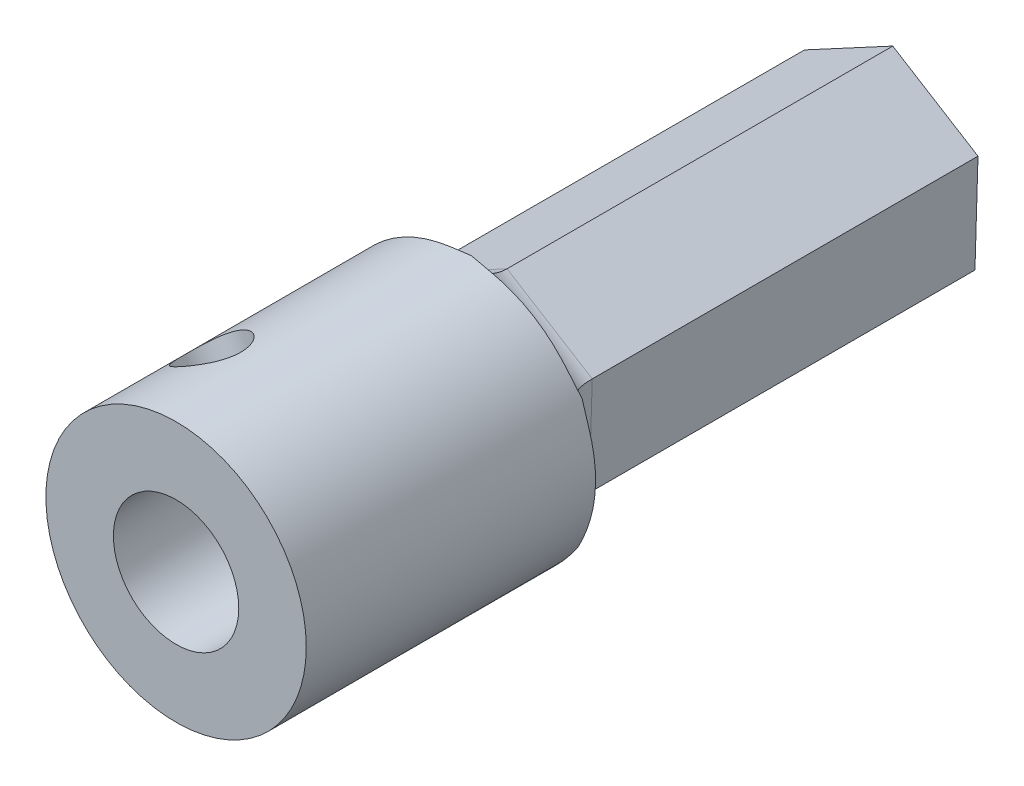
SolidWorks part; units mm, degrees
ref_plane "Front Plane" through (0, 0, 0) normal (0, 0, 1) x (1, 0, 0)
ref_plane "Top Plane" through (0, 0, 0) normal (0, 1, 0) x (1, 0, 0)
ref_plane "Right Plane" through (0, 0, 0) normal (1, 0, 0) x (0, 0, -1)
sketch "Sketch1" plane through (0, 0, 0) normal (0, 0, 1) x (1, 0, 0)
  line L1 (4.5768, 2.4602) -> (0.1578, 5.1938)
  line L2 (0.1578, 5.1938) -> (-4.419, 2.7335)
  line L3 (-4.419, 2.7335) -> (-4.5768, -2.4602)
  line L4 (-4.5768, -2.4602) -> (-0.1578, -5.1938)
  line L5 (-0.1578, -5.1938) -> (4.419, -2.7335)
  line L6 (4.419, -2.7335) -> (4.5768, 2.4602)
  circle A0 centre (0, 0) radius 4.5 construction
  dimension "D1" = 9
extrude "Boss-Extrude1" add sketch "Sketch1" along normal blind 22 contours L2 L3 L4 L5 L6 L1
sketch "Sketch2" plane through (0, 0, 22) normal (0, 0, 1) x (1, 0, 0)
  circle A0 centre (0, 0) radius 6.75
  dimension "D1" = 13.5
extrude "Boss-Extrude2" add sketch "Sketch2" along normal blind 15 contours A0
sketch "Sketch3" plane through (0, 0, 37) normal (0, 0, 1) x (1, 0, 0)
  circle A0 centre (0, 0) radius 3.25
  dimension "D1" = 6.5
extrude "Cut-Extrude1" cut sketch "Sketch3" against normal blind 15
fillet "Fillet2" radius 2 6 edges at (2.1306, -3.9636, 22) (4.4979, -0.1366, 22) (2.3673, 3.827, 22) (-2.1306, 3.9636, 22) (-4.4979, 0.1366, 22) (-2.3673, -3.827, 22)
sketch "Sketch8" plane through (2.1306, -3.9636, 0) normal (0.4735, -0.8808, 0) x (-0.8808, -0.4735, 0)
  line L0 (-3.25, -22) -> (3.25, -22) construction
  circle A0 centre (0, -32) radius 1.65
  dimension "D1" = 3.3
  dimension "D2" = 10
extrude "Cut-Extrude2" cut sketch "Sketch8" against normal blind 15 and the other way blind 15
sketch "Sketch9" plane through (0, 0, 0) normal (0, 0, -1) x (-1, 0, 0)
  circle A0 centre (0, 0) radius 1.65
  dimension "D1" = 3.3
extrude "Cut-Extrude3" cut sketch "Sketch9" against normal blind 23
